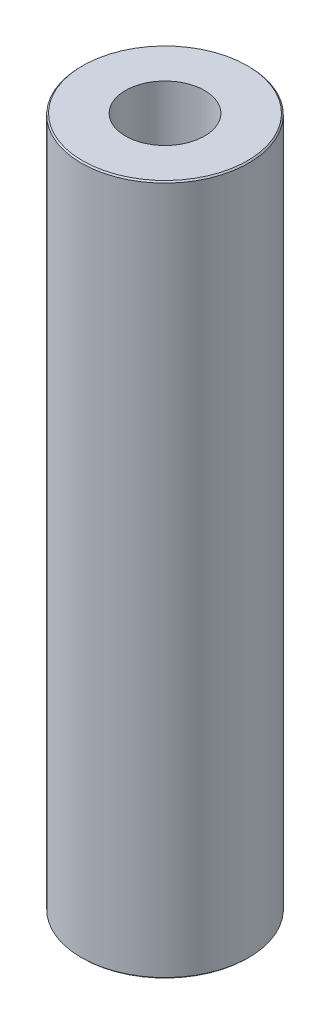
SolidWorks part; units mm, degrees
ref_plane "Front Plane" through (0, 0, 0) normal (0, 0, 1) x (1, 0, 0)
ref_plane "Top Plane" through (0, 0, 0) normal (0, 1, 0) x (1, 0, 0)
ref_plane "Right Plane" through (0, 0, 0) normal (1, 0, 0) x (0, 0, -1)
sketch "Sketch1" plane through (0, 0, 0) normal (0, 1, 0) x (1, 0, 0)
  circle A0 centre (0, 0) radius 60
  dimension "SHAFT_OD" = 120
extrude "Boss-Extrude1" add sketch "Sketch1" along normal blind 494.9899
sketch "Sketch2" plane through (0, 0, 0) normal (0, 1, 0) x (1, 0, 0)
  circle A0 centre (0, 0) radius 28.3336
  dimension "BORE_D" = 56.6672
extrude "Cut-Extrude1" cut sketch "Sketch2" along normal through all
chamfer "Chamfer1" distance 0.9591 angle 45 2 edges at (0, 494.9899, 60) (0, 0, 60)
